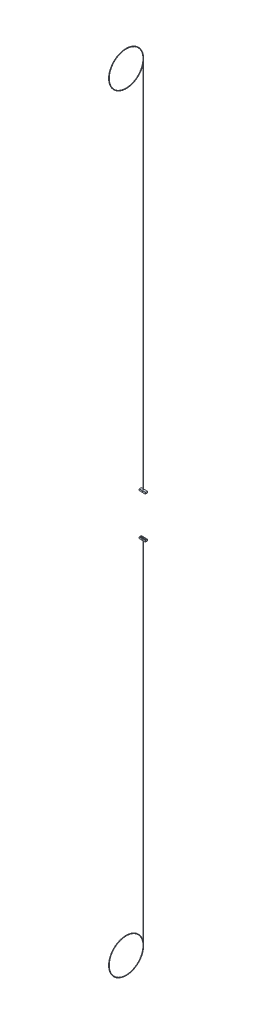
SolidWorks part; units mm, degrees
ref_plane "Front Plane" through (0, 0, 0) normal (0, 0, 1) x (1, 0, 0)
ref_plane "Top Plane" through (0, 0, 0) normal (0, 1, 0) x (1, 0, 0)
ref_plane "Right Plane" through (0, 0, 0) normal (1, 0, 0) x (0, 0, -1)
sketch "Sketch2" plane through (0, 0, 0) normal (1, 0, 0) x (0, 0, -1)
  circle A0 centre (0, 0) radius 41.275
  dimension "D1" = 82.55
sketch "Sketch3" plane through (0, 0, 0) normal (0, 0, 1) x (1, 0, 0)
  line L2 (0, -41.275) -> (0, 41.275) construction
  line L3 (0, -41.275) -> (0, 41.275)
  circle A0 centre (0, 41.91) radius 0.635
  dimension "D1" = 1.27
sweep "Sweep1" add profiles "Sketch3" path "Sketch2"
sketch "Sketch4" plane through (0, 0, 0) normal (0, 1, 0) x (1, 0, 0)
  line L1 (0, -41.275) -> (0, 41.275)
  line L2 (0, -41.275) -> (0, 41.275)
  circle A0 centre (0, 41.91) radius 0.635
  dimension "D2" = 1.27
  dimension "D1" = 0
extrude "Boss-Extrude1" add sketch "Sketch4" against normal blind 911.0725 contours A0
sketch "Sketch5" plane through (0, -911.0725, 0) normal (0, -1, 0) x (1, 0, 0)
  line L1 (-7.509, -44.43) -> (7.509, -44.43)
  line L2 (-7.509, -44.43) -> (-7.509, -39.39)
  line L3 (-7.509, -39.39) -> (7.509, -39.39)
  line L4 (7.509, -44.43) -> (7.509, -39.39)
  line L5 (-7.509, -44.43) -> (7.509, -39.39) construction
  line L6 (-7.509, -39.39) -> (7.509, -44.43) construction
  circle A0 centre (0, -41.91) radius 0.635 construction
  circle A1 centre (0, -41.91) radius 0.635
  dimension "D1" = 5.04
  dimension "D2" = 15.018
extrude "Boss-Extrude3" add sketch "Sketch5" along normal blind 3.81 contours L1 L4 L3 L2
shell "Shell1" thickness 1.27 removed face at (0, -914.8825, -41.91)
ref_plane "Plane1" through (0, -1012.3425, 0) normal (0, -1, 0) x (-1, 0, 0)
sketch "Sketch6" plane through (0, -1012.3425, 0) normal (0, -1, 0) x (-1, 0, 0)
  line L0 (7.509, 44.43) -> (7.509, 39.39) construction
  line L1 (7.509, 44.43) -> (-7.509, 44.43) construction
  line L2 (7.509, 39.39) -> (-7.509, 39.39) construction
  line L3 (7.509, 44.43) -> (7.509, 39.39)
  line L4 (7.509, 44.43) -> (-7.509, 44.43)
  line L5 (7.509, 39.39) -> (-7.509, 39.39)
  line L6 (-7.509, 44.43) -> (-7.509, 39.39) construction
  line L7 (-7.509, 44.43) -> (-7.509, 39.39)
extrude "Boss-Extrude4" add sketch "Sketch6" along normal blind 3.81 separate body
shell "Shell2" thickness 1.27 removed face at (0, -1012.3425, -41.91)
sketch "Sketch7" plane through (0, -1016.1525, 0) normal (0, -1, 0) x (1, 0, 0)
  circle A0 centre (0, -41.91) radius 0.635 construction
  circle A1 centre (0, -41.91) radius 0.635
extrude "Boss-Extrude5" add sketch "Sketch7" along normal blind 856.9449
sketch "Sketch8" plane through (0, 0, 0) normal (1, 0, 0) x (0, 0, -1)
  line L0 (0, 0) -> (0, -1873.0974) construction
  line L1 (0, -1873.0974) -> (41.91, -1873.0974) construction
  line L2 (41.275, -1873.0974) -> (42.545, -1873.0974) construction
  circle A0 centre (0, -1873.0974) radius 41.275
  dimension "D1" = 82.55
sketch "Sketch9" plane through (0, -1873.0974, 0) normal (0, -1, 0) x (1, 0, 0)
  circle A0 centre (0, -41.91) radius 0.635 construction
  circle A1 centre (0, -41.91) radius 0.635
sweep "Sweep2" add profiles "Sketch9" path "Sketch8"
sketch "Sketch10" plane through (0, 0, -39.39) normal (0, 0, 1) x (1, 0, 0)
  line L0 (0, -1013.6125) -> (0, -913.6125) construction
  line L1 (-7.509, -914.8825) -> (7.509, -914.8825) construction
  line L2 (7.509, -1012.3425) -> (-7.509, -1012.3425) construction
  circle A0 centre (0, -913.6125) radius 0.5969
  circle A1 centre (0, -1013.6125) radius 0.5969
  point P8 (0, -1012.3425)
  dimension "D1" = 1.1938
  dimension "D2" = 1.27
  dimension "D3" = 1.27
extrude "Cut-Extrude1" cut sketch "Sketch10" against normal through all
